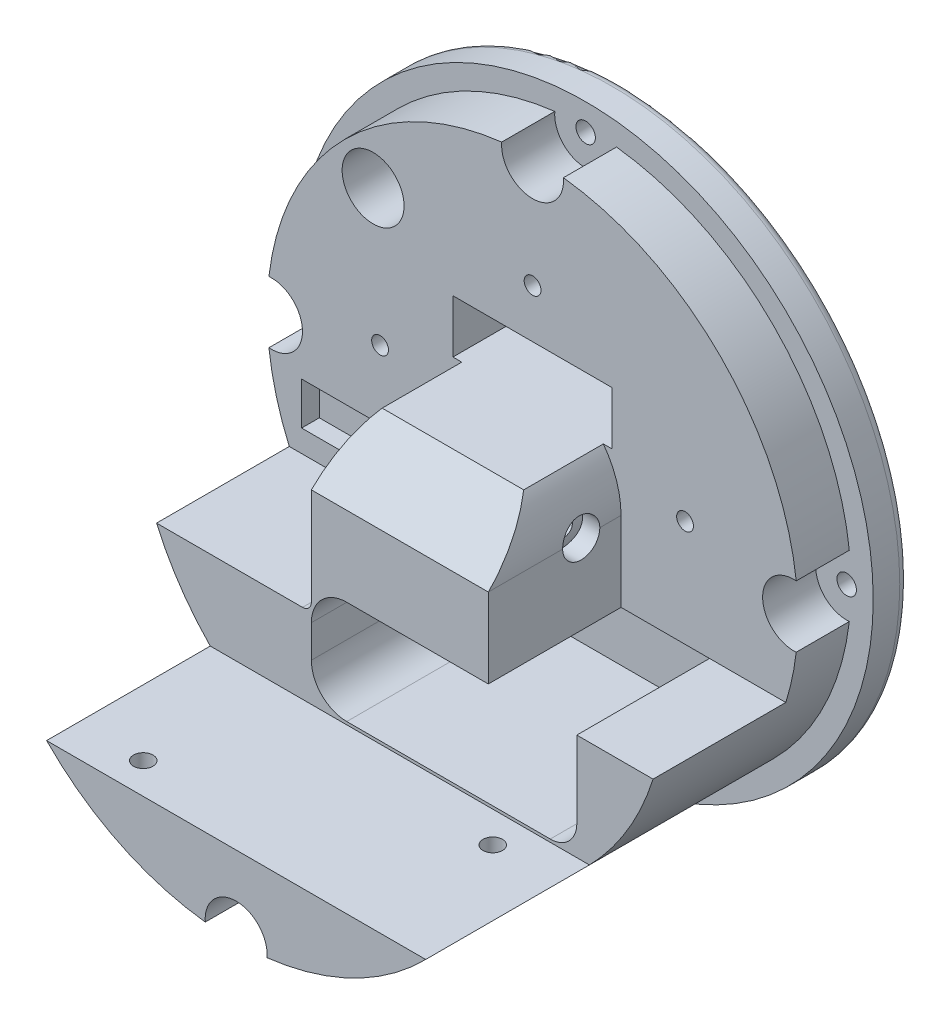
SolidWorks part; units mm, degrees
ref_plane "Front" through (0, 0, 0) normal (0, 0, 1) x (1, 0, 0)
ref_plane "Top" through (0, 0, 0) normal (0, 1, 0) x (1, 0, 0)
ref_plane "Right" through (0, 0, 0) normal (1, 0, 0) x (0, 0, -1)
sketch "草图3" plane through (0, 0, 0) normal (0, 0, 1) x (1, 0, 0)
  circle A0 centre (0, 0) radius 30
  dimension "D1" = 60
extrude "凸台-拉伸1" add sketch "草图3" along normal blind 10
sketch "草图8" plane through (0, 0, 10) normal (0, 0, 1) x (1, 0, 0)
  circle A0 centre (0, 0) radius 10
  dimension "D1" = 20
extrude "凸台-拉伸4" add sketch "草图8" along normal blind 15
sketch "草图9" plane through (0, 0, 0) normal (0, 0, -1) x (-1, 0, 0)
  circle A0 centre (0, 0) radius 4.05
  dimension "D1" = 8.1
extrude "切除-拉伸2" cut sketch "草图9" against normal blind 23
chamfer "倒角1" distance 4 angle 45 1 edges at (-4.05, 0, 23)
sketch "草图10" plane through (0, 0, 10) normal (0, 0, 1) x (1, 0, 0)
  line L0 (-28.6182, -9) -> (-4.3589, -9)
  line L1 (4.3589, -9) -> (28.6182, -9)
  arc A3 (-4.3589, -9) -> (4.3589, -9) centre (0, 0) ccw
  arc A6 (-28.6182, -9) -> (28.6182, -9) centre (0, 0) ccw
extrude "凸台-拉伸5" add sketch "草图10" along normal up to surface (15 mm away)
sketch "草图11" plane through (0, 0, 25) normal (0, 0, 1) x (1, 0, 0)
  line L0 (-21.4243, -21) -> (21.4243, -21)
  arc A0 (-21.4243, -21) -> (21.4243, -21) centre (0, 0) ccw
extrude "凸台-拉伸6" add sketch "草图11" along normal offset from surface (18.5 mm away) 2
sketch "草图12" plane through (0, 0, 25) normal (0, 0, 1) x (1, 0, 0)
  line L0 (-2.106, -15.674) -> (2.106, -15.674)
  line L3 (-2.106, -20.674) -> (2.106, -20.674)
  arc A4 (-2.106, -15.674) -> (-2.106, -20.674) centre (-2.106, -18.174) ccw
  arc A5 (2.106, -20.674) -> (2.106, -15.674) centre (2.106, -18.174) ccw
  dimension "D1" = 5
  dimension "D2" = 5
extrude "切除-拉伸3" cut sketch "草图12" against normal up to surface (15 mm away) up to face at (0, 5.5, 10)
sketch "草图13" plane through (0, -21, 0) normal (0, 1, 0) x (1, 0, 0)
  circle A0 centre (14, -28.5) radius 1.1
  circle A1 centre (-14, -40) radius 1.1
  dimension "D1" = 2.2
  dimension "D2" = 2.2
extrude "切除-拉伸4" cut sketch "草图13" against normal blind 22
sketch "草图14" plane through (0, 0, 10) normal (0, 0, 1) x (1, 0, 0)
  line L0 (-10, 0) -> (-10, -9)
  line L1 (-4.3589, -9) -> (-28.6182, -9) construction
  line L2 (-10, -9) -> (-4.3589, -9)
  line L3 (10, 0) -> (10, -9)
  line L4 (28.6182, -9) -> (4.3589, -9) construction
  line L5 (4.3589, -9) -> (10, -9)
  arc A0 (4.3589, -9) -> (10, 0) centre (0, 0) ccw
  arc A1 (-10, 0) -> (-4.3589, -9) centre (0, 0) ccw
extrude "凸台-拉伸7" add sketch "草图14" along normal up to surface (15 mm away) up to face at (0, -18.174, 25)
sketch "草图15" plane through (10, 0, 0) normal (1, 0, 0) x (0, 0, -1)
  line L0 (-25, 0) -> (-15, 10)
  line L1 (-25, 10) -> (-25, 0) construction
  line L2 (-10, 10) -> (-25, 10) construction
  line L3 (-15, 10) -> (-25, 10)
  line L4 (-25, 10) -> (-25, 0)
extrude "切除-拉伸5" cut sketch "草图15" against normal blind 22
sketch "草图16" plane through (0, 0, 0) normal (0, 0, -1) x (-1, 0, 0)
  circle A0 centre (0, 0) radius 32.5
  circle A1 centre (0, 0) radius 30
  dimension "D1" = 65
extrude "凸台-拉伸8" add sketch "草图16" against normal blind 4
sketch "草图17" plane through (0, 0, 25) normal (0, 0, 1) x (1, 0, 0)
  line L0 (2.106, -15.674) -> (13, -15.674)
  line L1 (16, -12.674) -> (16, -9)
  line L2 (28.6182, -9) -> (10, -9) construction
  line L3 (16, -9) -> (20, -9)
  line L4 (20, -9) -> (20, -17.674)
  line L5 (17, -20.674) -> (2.106, -20.674)
  line L6 (-2.106, -20.674) -> (2.106, -20.674) construction
  line L7 (2.106, -20.674) -> (2.106, -15.674)
  line L8 (10, -9) -> (10, 0) construction
  arc A0 (2.106, -20.674) -> (2.106, -15.674) centre (2.106, -18.174) ccw construction
  arc A1 (13, -15.674) -> (16, -12.674) centre (13, -12.674) ccw
  arc A2 (20, -17.674) -> (17, -20.674) centre (17, -17.674) cw
  dimension "D3" = 3
  dimension "D1" = 4
  dimension "D2" = 6
extrude "切除-拉伸6" cut sketch "草图17" against normal up to surface (15 mm away) up to face at (0, 2.1667, 10)
fillet "圆角1" radius 1 1 edges at (-32.5, 0, 0)
sketch "草图18" plane through (0, 0, 43.5) normal (0, 0, 1) x (1, 0, 0)
  circle A0 centre (29.5, 0) radius 3.5
  circle A1 centre (0, 29.5) radius 3.5
  circle A2 centre (-29.5, 0) radius 3.5
  circle A3 centre (0, -29.5) radius 3.5
  dimension "D1" = 7
  dimension "D2" = 7
  dimension "D3" = 7
  dimension "D4" = 7
extrude "切除-拉伸7" cut sketch "草图18" against normal up to surface (39.5 mm away) up to face at (-30, 0, 4)
sketch "草图19" plane through (0, 0, 0) normal (0, 0, -1) x (-1, 0, 0)
  circle A0 centre (0, 29.5) radius 1.1
  circle A1 centre (-29.5, 0) radius 1.1
  circle A2 centre (0, -29.5) radius 1.1
  circle A3 centre (29.5, 0) radius 1.1
  dimension "D1" = 2.2
  dimension "D2" = 2.2
  dimension "D3" = 2.2
  dimension "D4" = 2.2
extrude "切除-拉伸8" cut sketch "草图19" against normal blind 10
sketch "草图20" plane through (-10, 0, 0) normal (-1, 0, 0) x (0, 0, 1)
  line L0 (25, 0) -> (10, 0) construction
  line L1 (10, -3.5) -> (10, 3.5) construction
  circle A0 centre (14.5, 0) radius 0.95
  dimension "D1" = 1.9
  dimension "D2" = 4.5
extrude "切除-拉伸9" cut sketch "草图20" against normal blind 25
ref_plane "基准面1" through (0, -30, 0) normal (0, 1, 0) x (1, 0, 0)
sketch "草图22" plane through (0, -30, 0) normal (0, 1, 0) x (1, 0, 0)
  circle A0 centre (14, -28.5) radius 2.1
  circle A1 centre (-14, -40) radius 2.1
  dimension "D1" = 4.2
  dimension "D2" = 4.2
extrude "切除-拉伸10" cut sketch "草图22" along normal offset from surface (6 mm away) 3 up to face at (12.9, -21, 28.5)
sketch "草图23" plane through (0, 0, 0) normal (0, 0, -1) x (-1, 0, 0)
  circle A0 centre (29.5, 0) radius 2.1
  circle A1 centre (0, -29.5) radius 2.1
  circle A2 centre (0, 29.5) radius 2.1
  circle A3 centre (-29.5, 0) radius 2.1
  dimension "D1" = 4.2
  dimension "D2" = 4.2
  dimension "D3" = 4.2
  dimension "D4" = 4.2
extrude "切除-拉伸11" cut sketch "草图23" against normal offset from surface (2 mm away) 2 up to face at (-1.1, 29.5, 4)
sketch "草图24" plane through (-10, 0, 0) normal (-1, 0, 0) x (0, 0, 1)
  circle A0 centre (14.5, 0) radius 2.1
  dimension "D1" = 4.2
extrude "切除-拉伸12" cut sketch "草图24" against normal offset from surface (1.95 mm away) 4
sketch "草图25" plane through (10, 0, 0) normal (1, 0, 0) x (0, 0, -1)
  circle A0 centre (-14.5, 0) radius 2.1
  dimension "D1" = 4.2
extrude "切除-拉伸13" cut sketch "草图25" against normal offset from surface (2.2287 mm away) 4
sketch "草图26" plane through (0, 0, 25) normal (0, 0, 1) x (1, 0, 0)
  line L1 (-9, 6) -> (9, 6)
  line L2 (-9, 6) -> (-9, 12)
  line L3 (-9, 12) -> (9, 12)
  line L4 (9, 6) -> (9, 12)
  dimension "D1" = 18
  dimension "D2" = 6
  dimension "D3" = 9
  dimension "D4" = 6
extrude "切除-拉伸14" cut sketch "草图26" against normal blind 28
sketch "草图27" plane through (0, 0, 25) normal (0, 0, 1) x (1, 0, 0)
  line L0 (-10, 0) -> (10, 0) construction
  line L1 (-10, -9) -> (-28.6182, -9)
  line L2 (-10, 0) -> (-10, -9) construction
  line L3 (-10, -9) -> (-28.6182, -9) construction
  line L4 (-10, -9) -> (-10, -12)
  line L5 (-10, -12) -> (-27.4955, -12)
  arc A0 (-28.6182, -9) -> (-27.4955, -12) centre (0, 0) ccw
  dimension "D1" = 3
extrude "切除-拉伸15" cut sketch "草图27" against normal up to surface (15 mm away) up to face at (3.7127, -1.7338, 10)
sketch "草图28" plane through (0, 0, 10) normal (0, 0, 1) x (1, 0, 0)
  circle A0 centre (-18.0216, 18.0216) radius 3.5
  dimension "D1" = 7
extrude "切除-拉伸16" cut sketch "草图28" against normal blind 9
sketch "草图29" plane through (0, 0, 1) normal (0, 0, 1) x (1, 0, 0)
  circle A0 centre (-18.0216, 18.0216) radius 2
  dimension "D1" = 4
extrude "切除-拉伸17" cut sketch "草图29" against normal blind 9
sketch "草图30" plane through (0, 0, 10) normal (0, 0, 1) x (1, 0, 0)
  circle A0 centre (0, 17.5) radius 0.95
  circle A1 centre (-17.2341, 3.0388) radius 0.95
  circle A2 centre (17.2341, 3.0388) radius 0.95
  dimension "D1" = 1.9
  dimension "D2" = 1.9
  dimension "D3" = 1.9
extrude "切除-拉伸18" cut sketch "草图30" against normal blind 6
sketch "草图31" plane through (0, 0, 10) normal (0, 0, 1) x (1, 0, 0)
  line L0 (-26.1, -4.7) -> (-12, -4.7)
  line L1 (-12, -4.7) -> (-12, -9.5)
  line L2 (-12, -9.5) -> (-26.1, -9.5)
  line L3 (-26.1, -9.5) -> (-26.1, -4.7)
extrude "切除-拉伸19" cut sketch "草图31" against normal blind 2
sketch "草图32" plane through (0, 0, 25) normal (0, 0, 1) x (1, 0, 0)
  line L0 (20, -9) -> (20, -17.674)
  line L1 (17, -20.674) -> (-6, -20.674)
  line L2 (-10, -16.674) -> (-10, -13)
  line L3 (-10, 0) -> (-10, -12) construction
  line L4 (-6, -9) -> (20, -9)
  arc A0 (20, -17.674) -> (17, -20.674) centre (17, -17.674) cw
  arc A1 (-6, -20.674) -> (-10, -16.674) centre (-6, -16.674) cw
  arc A2 (-10, -13) -> (-6, -9) centre (-6, -13) cw
  point P15 (-10, -9)
  dimension "D1" = 3
  dimension "D2" = 4
extrude "切除-拉伸20" cut sketch "草图32" against normal offset from surface (21 mm away) 6 up to face at (-19.05, -7.1, 10) offset beyond the face yes
fillet "圆角2" radius 1 1 edges at (-10, -12, 17.5)
